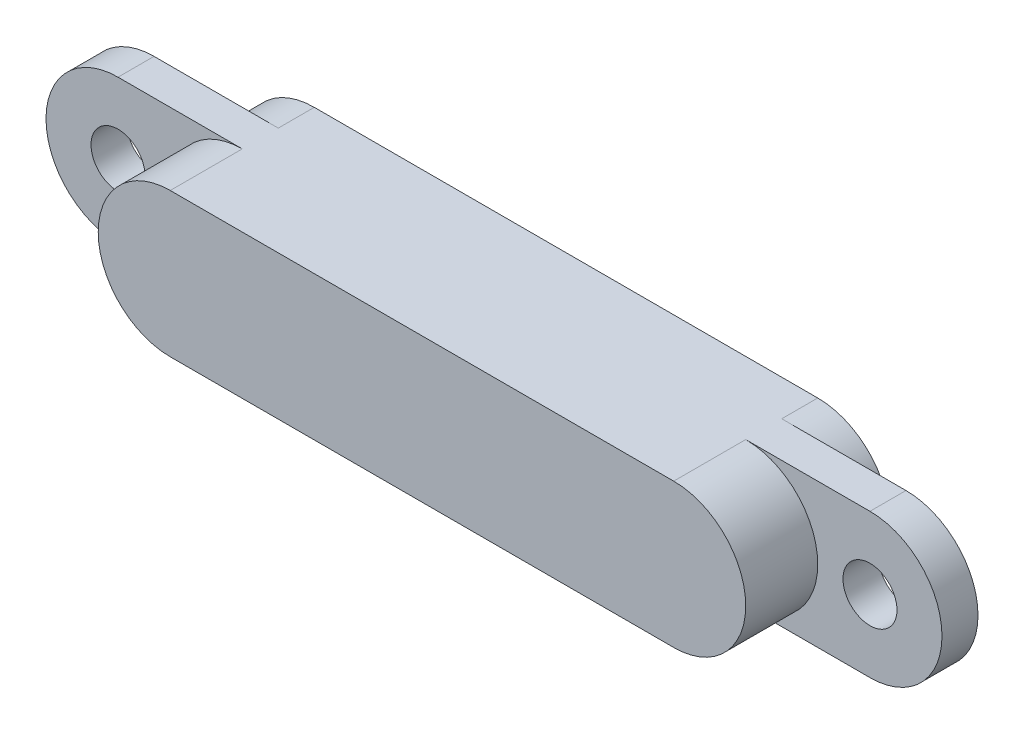
SolidWorks part; units mm, degrees
ref_plane "Front Plane" through (0, 0, 0) normal (0, 0, 1) x (1, 0, 0)
ref_plane "Top Plane" through (0, 0, 0) normal (0, 1, 0) x (1, 0, 0)
ref_plane "Right Plane" through (0, 0, 0) normal (1, 0, 0) x (0, 0, -1)
sketch "Sketch1" plane through (0, 0, 0) normal (0, 0, 1) x (1, 0, 0)
  line L0 (-10.44, 0) -> (10.44, 0) construction
  line L1 (-10.44, 2) -> (10.44, 2)
  line L2 (-10.44, -2) -> (10.44, -2)
  arc A0 (-10.44, 2) -> (-10.44, -2) centre (-10.44, 0) ccw
  arc A1 (10.44, -2) -> (10.44, 2) centre (10.44, 0) ccw
  point P3 (0, 0)
  dimension "D1" = 20.88
  dimension "D2" = 4
extrude "Boss-Extrude1" add sketch "Sketch1" along normal blind 4
sketch "Sketch2" plane through (0, 0, 4) normal (0, 0, 1) x (1, 0, 0)
  circle A0 centre (-10.44, 0) radius 0.75
  circle A1 centre (10.44, 0) radius 0.75
  dimension "D1" = 1.5
extrude "Cut-Extrude1" cut sketch "Sketch2" against normal blind 4
sketch "Sketch4" plane through (0, 0, 4) normal (0, 0, 1) x (1, 0, 0)
  line L0 (-6.99, 0) -> (6.99, 0) construction
  line L1 (-6.99, 2) -> (6.99, 2)
  line L2 (-6.99, -2) -> (6.99, -2)
  line L3 (10.44, 2) -> (-10.44, 2) construction
  arc A0 (-6.99, 2) -> (-6.99, -2) centre (-6.99, 0) ccw
  arc A1 (6.99, -2) -> (6.99, 2) centre (6.99, 0) ccw
  point P2 (0, 0)
  point P7 (0, 0)
  point P8 (-7.3307, 0)
  point P10 (-7.0181, 2)
  circle M5 centre (-10.44, 0) radius 0.75
  circle M6 centre (10.44, 0) radius 0.75
  arc M7 (-10.44, 2) -> (-10.44, -2) centre (-10.44, 0) ccw
  line M8 (-10.44, -2) -> (10.44, -2)
  arc M9 (10.44, -2) -> (10.44, 2) centre (10.44, 0) ccw
  line M10 (10.44, 2) -> (-10.44, 2)
  dimension "D1" = 17.98
extrude "Cut-Extrude2" cut sketch "Sketch4" against normal blind 2 contours A0 M10 M7 M8 M5 | A1 M8 M9 M10 M6 region at (-9.0576, 0, 4) region at (8.715, 1.9324, 4)
extrude "Cut-Extrude3" cut sketch "Sketch4<3>" against normal blind 1 from offset 3 contours A0 M10 M7 M8 M5 | A1 M8 M9 M10 M6 region at (-9.0576, 0, 4) region at (8.715, 1.9324, 4) offset against normal yes
sketch "Sketch4<3>" plane through (0, 0, 4) normal (0, 0, 1) x (1, 0, 0) same geometry as "Sketch4"
